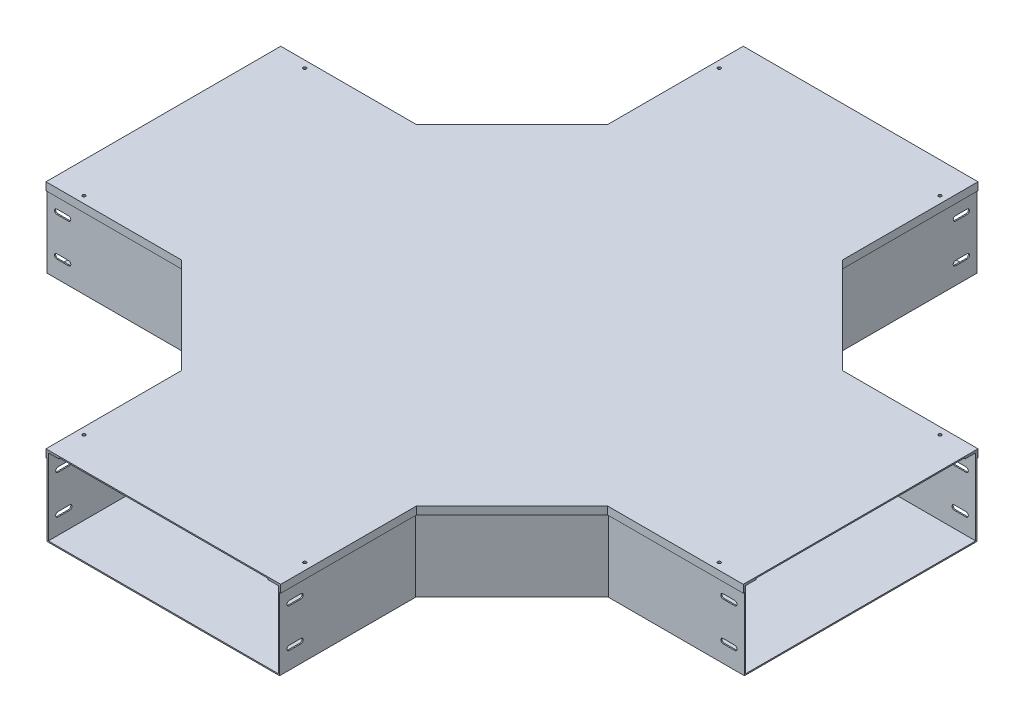
SolidWorks part; units mm, degrees
material "Plain Carbon Steel"
ref_plane "Front Plane" through (0, 0, 0) normal (0, 0, 1) x (1, 0, 0)
ref_plane "Top Plane" through (0, 0, 0) normal (0, 1, 0) x (1, 0, 0)
ref_plane "Right Plane" through (0, 0, 0) normal (1, 0, 0) x (0, 0, -1)
ref_plane "Plane1" through (0, -50, 0) normal (0, 1, 0) x (1, 0, 0)
sketch "Sketch1" plane through (0, -50, 0) normal (0, 1, 0) x (1, 0, 0)
  line L0 (-150, 450) -> (150, 450)
  line L1 (-150, -450) -> (150, -450)
  line L2 (450, 150) -> (450, -150)
  line L3 (-450, 150) -> (-450, -150)
  line L4 (150, -450) -> (150, -274.2641)
  line L5 (450, -150) -> (274.2641, -150)
  line L6 (150, 450) -> (150, 274.2641)
  line L7 (-150, 450) -> (-150, 274.2641)
  line L8 (-450, 150) -> (-274.2641, 150)
  line L9 (-450, -150) -> (-274.2641, -150)
  line L10 (-150, -450) -> (-150, -274.2641)
  line L11 (450, 150) -> (274.2641, 150)
  line L12 (0, 450) -> (0, -450) construction
  line L13 (-450, 0) -> (450, 0) construction
  line L14 (150, 274.2641) -> (274.2641, 150)
  line L15 (-274.2641, 150) -> (-150, 274.2641)
  line L16 (-274.2641, -150) -> (-150, -274.2641)
  line L17 (150, -274.2641) -> (274.2641, -150)
  dimension "Width" = 300
  dimension "Length" = 900
extrude "Boss-Extrude1" add sketch "Sketch1" along normal blind 1.5
sketch "Sketch2" plane through (0, -50, 0) normal (0, -1, 0) x (-1, 0, 0)
  line L0 (-150, -450) -> (-150, -274.2641) construction
  line L1 (-274.2641, -150) -> (-450, -150) construction
  line L2 (-150, -450) -> (-150, -274.2641)
  line L3 (-274.2641, -150) -> (-450, -150)
  line L4 (-450, 150) -> (-274.2641, 150) construction
  line L5 (-150, 274.2641) -> (-150, 450) construction
  line L6 (150, 450) -> (150, 274.2641) construction
  line L7 (274.2641, 150) -> (450, 150) construction
  line L8 (450, -150) -> (274.2641, -150) construction
  line L9 (150, -274.2641) -> (150, -450) construction
  line L10 (-450, 150) -> (-274.2641, 150)
  line L11 (-150, 274.2641) -> (-150, 450)
  line L12 (150, 450) -> (150, 274.2641)
  line L13 (274.2641, 150) -> (450, 150)
  line L14 (450, -150) -> (274.2641, -150)
  line L15 (150, -274.2641) -> (150, -450)
  line L16 (274.2641, 150) -> (150, 274.2641)
  line L17 (274.2641, -150) -> (150, -274.2641)
  line L18 (-150, -274.2641) -> (-274.2641, -150)
  line L19 (-274.2641, 150) -> (-150, 274.2641)
extrude "Extrude-Thin1" add sketch "Sketch2" against normal blind 100 thin thin type one direction wall 1.5
sketch "Sketch3" plane through (0, 0, 0) normal (0, 0, 1) x (1, 0, 0)
  line L0 (422.5, 25) -> (437.5, 25) construction
  line L1 (422.5, 28) -> (437.5, 28)
  line L2 (422.5, 22) -> (437.5, 22)
  line L3 (422.5, -25) -> (437.5, -25) construction
  line L4 (422.5, -22) -> (437.5, -22)
  line L5 (422.5, -28) -> (437.5, -28)
  line L6 (410, 0) -> (450, 0) construction
  line L7 (450, -48.5) -> (450, 50) construction
  line L8 (-437.5, 25) -> (-422.5, 25) construction
  line L9 (430, -50) -> (430, 0) construction
  line L10 (-437.5, 28) -> (-422.5, 28)
  line L11 (430, 0) -> (430, 50) construction
  line L12 (-437.5, 22) -> (-422.5, 22)
  line L13 (-437.5, -25) -> (-422.5, -25) construction
  line L14 (-437.5, -22) -> (-422.5, -22)
  line L15 (-437.5, -28) -> (-422.5, -28)
  line L16 (-450, 0) -> (-410, 0) construction
  line L17 (-430, -50) -> (-430, 0) construction
  line L18 (-430, 0) -> (-430, 50) construction
  line L19 (-450, 50) -> (-450, -48.5) construction
  arc A0 (422.5, 28) -> (422.5, 22) centre (422.5, 25) ccw
  arc A1 (437.5, 22) -> (437.5, 28) centre (437.5, 25) ccw
  arc A2 (422.5, -22) -> (422.5, -28) centre (422.5, -25) ccw
  arc A3 (437.5, -28) -> (437.5, -22) centre (437.5, -25) ccw
  arc A4 (-437.5, 28) -> (-437.5, 22) centre (-437.5, 25) ccw
  arc A5 (-422.5, 22) -> (-422.5, 28) centre (-422.5, 25) ccw
  arc A6 (-437.5, -22) -> (-437.5, -28) centre (-437.5, -25) ccw
  arc A7 (-422.5, -28) -> (-422.5, -22) centre (-422.5, -25) ccw
  point P2 (430, 25)
  point P8 (430, -25)
  point P22 (-430, 25)
  point P30 (-430, -25)
  dimension "D1" = 3
  dimension "D2" = 15
  dimension "D3" = 50
  dimension "D4" = 40
  dimension "D5" = 50
extrude "Cut-Extrude1" cut sketch "Sketch3" against normal through all and the other way through all
sketch "Sketch4" plane through (0, 0, 0) normal (1, 0, 0) x (0, 0, -1)
  line L0 (-450, 0) -> (-410, 0) construction
  line L1 (-450, -48.5) -> (-450, 50) construction
  line L2 (410, 0) -> (450, 0) construction
  line L3 (-430, 50) -> (-430, 0) construction
  line L4 (430, 50) -> (430, 0) construction
  line L5 (-430, 0) -> (-430, -50) construction
  line L6 (430, 0) -> (430, -50) construction
  line L7 (-437.5, 25) -> (-422.5, 25) construction
  line L8 (-437.5, 28) -> (-422.5, 28)
  line L9 (-437.5, 22) -> (-422.5, 22)
  line L10 (-437.5, -25) -> (-422.5, -25) construction
  line L11 (-437.5, -22) -> (-422.5, -22)
  line L12 (-437.5, -28) -> (-422.5, -28)
  line L13 (422.5, 25) -> (437.5, 25) construction
  line L14 (422.5, 28) -> (437.5, 28)
  line L15 (422.5, 22) -> (437.5, 22)
  line L16 (422.5, -25) -> (437.5, -25) construction
  line L17 (422.5, -22) -> (437.5, -22)
  line L18 (422.5, -28) -> (437.5, -28)
  line L19 (450, 50) -> (450, -48.5) construction
  arc A0 (-437.5, 28) -> (-437.5, 22) centre (-437.5, 25) ccw
  arc A1 (-422.5, 22) -> (-422.5, 28) centre (-422.5, 25) ccw
  arc A2 (-437.5, -22) -> (-437.5, -28) centre (-437.5, -25) ccw
  arc A3 (-422.5, -28) -> (-422.5, -22) centre (-422.5, -25) ccw
  arc A4 (422.5, 28) -> (422.5, 22) centre (422.5, 25) ccw
  arc A5 (437.5, 22) -> (437.5, 28) centre (437.5, 25) ccw
  arc A6 (422.5, -22) -> (422.5, -28) centre (422.5, -25) ccw
  arc A7 (437.5, -28) -> (437.5, -22) centre (437.5, -25) ccw
  point P15 (-430, 25)
  point P21 (-430, -25)
  point P29 (430, 25)
  point P35 (430, -25)
  dimension "D1" = 3
  dimension "D2" = 15
  dimension "D5" = 50
  dimension "D3" = 40
  dimension "D4" = 50
extrude "Cut-Extrude2" cut sketch "Sketch4" against normal through all and the other way through all
sketch "Sketch5" plane through (0, 50, 0) normal (0, 1, 0) x (1, 0, 0)
  line L0 (450, 135) -> (268.0509, 135)
  line L1 (268.0509, 135) -> (135, 268.0509)
  line L2 (135, 268.0509) -> (135, 450)
  line L3 (-135, 450) -> (-135, 268.0509)
  line L4 (-135, 268.0509) -> (-268.0509, 135)
  line L5 (-268.0509, 135) -> (-450, 135)
  line L6 (-450, -135) -> (-268.0509, -135)
  line L7 (-268.0509, -135) -> (-135, -268.0509)
  line L8 (-135, -268.0509) -> (-135, -450)
  line L9 (135, -450) -> (135, -268.0509)
  line L10 (135, -268.0509) -> (268.0509, -135)
  line L11 (268.0509, -135) -> (450, -135)
  line L12 (-450, -150) -> (-450, -135)
  line L13 (-450, 135) -> (-450, 150)
  line L14 (-135, 450) -> (-150, 450)
  line L15 (150, 450) -> (135, 450)
  line L16 (274.2641, 150) -> (150, 274.2641)
  line L17 (150, 274.2641) -> (150, 450)
  line L18 (150, 450) -> (-150, 450)
  line L19 (-150, 450) -> (-150, 274.2641)
  line L20 (-150, 274.2641) -> (-274.2641, 150)
  line L21 (-274.2641, 150) -> (-450, 150)
  line L22 (-450, 150) -> (-450, -150)
  line L23 (-450, -150) -> (-274.2641, -150)
  line L24 (-274.2641, -150) -> (-150, -274.2641)
  line L25 (-150, -274.2641) -> (-150, -450)
  line L26 (-150, -450) -> (150, -450)
  line L27 (150, -450) -> (150, -274.2641)
  line L28 (150, -274.2641) -> (274.2641, -150)
  line L29 (274.2641, -150) -> (450, -150)
  line L30 (450, -150) -> (450, 150)
  line L31 (450, 150) -> (274.2641, 150)
  line L32 (274.2641, 150) -> (150, 274.2641)
  line L33 (150, 274.2641) -> (150, 450)
  line L34 (450, 135) -> (450, 150)
  line L35 (-150, 450) -> (-150, 274.2641)
  line L36 (-150, 274.2641) -> (-274.2641, 150)
  line L37 (-274.2641, 150) -> (-450, 150)
  line L38 (450, -150) -> (450, -135)
  line L39 (-450, -150) -> (-274.2641, -150)
  line L40 (-274.2641, -150) -> (-150, -274.2641)
  line L41 (-150, -274.2641) -> (-150, -450)
  line L42 (135, -450) -> (150, -450)
  line L43 (150, -450) -> (150, -274.2641)
  line L44 (150, -274.2641) -> (274.2641, -150)
  line L45 (274.2641, -150) -> (450, -150)
  line L46 (-150, -450) -> (-135, -450)
  line L47 (450, 150) -> (274.2641, 150)
  dimension "D1" = 0
  dimension "D2" = 15
extrude "Boss-Extrude2" add sketch "Sketch5" along normal blind 1.5
sketch "Sketch6" plane through (0, 51.5, 0) normal (0, 1, 0) x (1, 0, 0)
  line L0 (-450, 150) -> (-450, 135) construction
  line L1 (-450, -135) -> (-450, -150) construction
  line L2 (450, 135) -> (450, 150) construction
  line L3 (450, -150) -> (450, -135) construction
  line L4 (-150, -450) -> (-135, -450) construction
  line L5 (135, -450) -> (150, -450) construction
  line L6 (-135, 450) -> (-150, 450) construction
  line L7 (150, 450) -> (135, 450) construction
  circle A0 centre (-410, -142.5) radius 2
  circle A1 centre (-410, 142.5) radius 2
  circle A2 centre (-142.5, 410) radius 2
  circle A3 centre (142.5, 410) radius 2
  circle A4 centre (410, 142.5) radius 2
  circle A5 centre (410, -142.5) radius 2
  circle A6 centre (142.5, -410) radius 2
  circle A7 centre (-142.5, -410) radius 2
  point P18 (-450, 142.5)
  point P21 (-450, -142.5)
  point P24 (450, 142.5)
  point P27 (450, -142.5)
  point P32 (142.5, -450)
  point P33 (-142.5, -450)
  point P36 (-142.5, 450)
  point P39 (142.5, 450)
  dimension "D1" = 40
  dimension "D5" = 4
  dimension "D2" = 40
  dimension "D3" = 40
  dimension "D4" = 40
extrude "Cut-Extrude3" cut sketch "Sketch6" against normal up to next
sketch "Sketch7" plane through (0, 51.5, 0) normal (0, 1, 0) x (1, 0, 0)
  line L16 (274.2641, 150) -> (150, 274.2641)
  line L17 (150, 274.2641) -> (150, 450)
  line L18 (150, 450) -> (-150, 450)
  line L19 (-150, 450) -> (-150, 274.2641)
  line L20 (-150, 274.2641) -> (-274.2641, 150)
  line L21 (-274.2641, 150) -> (-450, 150)
  line L22 (-450, 150) -> (-450, -150)
  line L23 (-450, -150) -> (-274.2641, -150)
  line L24 (-274.2641, -150) -> (-150, -274.2641)
  line L25 (-150, -274.2641) -> (-150, -450)
  line L26 (-150, -450) -> (150, -450)
  line L27 (150, -450) -> (150, -274.2641)
  line L28 (150, -274.2641) -> (274.2641, -150)
  line L29 (274.2641, -150) -> (450, -150)
  line L30 (450, -150) -> (450, 150)
  line L31 (450, 150) -> (274.2641, 150)
  line L32 (274.2641, 150) -> (150, 274.2641)
  line L33 (150, 274.2641) -> (150, 450)
  line L34 (150, 450) -> (-150, 450)
  line L35 (-150, 450) -> (-150, 274.2641)
  line L36 (-150, 274.2641) -> (-274.2641, 150)
  line L37 (-274.2641, 150) -> (-450, 150)
  line L38 (-450, 150) -> (-450, -150)
  line L39 (-450, -150) -> (-274.2641, -150)
  line L40 (-274.2641, -150) -> (-150, -274.2641)
  line L41 (-150, -274.2641) -> (-150, -450)
  line L42 (-150, -450) -> (150, -450)
  line L43 (150, -450) -> (150, -274.2641)
  line L44 (150, -274.2641) -> (274.2641, -150)
  line L45 (274.2641, -150) -> (450, -150)
  line L46 (450, -150) -> (450, 150)
  line L47 (450, 150) -> (274.2641, 150)
  dimension "D1" = 0
extrude "Boss-Extrude3" add sketch "Sketch7" along normal blind 1.5 separate body
sketch "Sketch8" plane through (0, 53, 0) normal (0, 1, 0) x (1, 0, 0)
  line L0 (150, 274.2641) -> (150, 450) construction
  line L1 (274.2641, 150) -> (150, 274.2641) construction
  line L2 (450, 150) -> (274.2641, 150) construction
  line L3 (274.2641, -150) -> (450, -150) construction
  line L4 (150, -274.2641) -> (274.2641, -150) construction
  line L5 (150, -450) -> (150, -274.2641) construction
  line L6 (-150, -274.2641) -> (-150, -450) construction
  line L7 (-274.2641, -150) -> (-150, -274.2641) construction
  line L8 (-450, -150) -> (-274.2641, -150) construction
  line L9 (-274.2641, 150) -> (-450, 150) construction
  line L10 (-150, 274.2641) -> (-274.2641, 150) construction
  line L11 (-150, 450) -> (-150, 274.2641) construction
  line L12 (150, 274.2641) -> (150, 450)
  line L13 (274.2641, 150) -> (150, 274.2641)
  line L14 (450, 150) -> (274.2641, 150)
  line L15 (274.2641, -150) -> (450, -150)
  line L16 (150, -274.2641) -> (274.2641, -150)
  line L17 (150, -450) -> (150, -274.2641)
  line L18 (-150, -274.2641) -> (-150, -450)
  line L19 (-274.2641, -150) -> (-150, -274.2641)
  line L20 (-450, -150) -> (-274.2641, -150)
  line L21 (-274.2641, 150) -> (-450, 150)
  line L22 (-150, 274.2641) -> (-274.2641, 150)
  line L23 (-150, 450) -> (-150, 274.2641)
extrude "Extrude-Thin2" add sketch "Sketch8" against normal blind 10 thin thin type one direction wall 1.5
sketch "Sketch9" plane through (0, 53, 0) normal (0, 1, 0) x (1, 0, 0)
  circle A1 centre (-142.5, -410) radius 2
  circle A2 centre (-142.5, -410) radius 2
  circle A3 centre (142.5, -410) radius 2
  circle A4 centre (142.5, -410) radius 2
  circle A5 centre (410, -142.5) radius 2
  circle A6 centre (410, -142.5) radius 2
  circle A7 centre (410, 142.5) radius 2
  circle A8 centre (410, 142.5) radius 2
  circle A9 centre (142.5, 410) radius 2
  circle A10 centre (142.5, 410) radius 2
  circle A11 centre (-142.5, 410) radius 2
  circle A12 centre (-142.5, 410) radius 2
  circle A13 centre (-410, 142.5) radius 2
  circle A14 centre (-410, 142.5) radius 2
  circle A15 centre (-410, -142.5) radius 2
  circle A16 centre (-410, -142.5) radius 2
  dimension "D1" = 0
  dimension "D2" = 0
  dimension "D3" = 0
  dimension "D4" = 0
  dimension "D5" = 0
  dimension "D6" = 0
  dimension "D7" = 0
  dimension "D8" = 0
extrude "Cut-Extrude4" cut sketch "Sketch9" against normal up to next (1.5 mm away)
sketch "Sketch10" plane through (0, 0, 0) normal (0, -1, 0) x (-1, 0, 0)
  line L0 (150, -450) -> (-150, -450) construction
  line L1 (-450, -150) -> (-450, 150) construction
  line L2 (150, 450) -> (-150, 450) construction
  line L3 (450, -150) -> (450, 150) construction
  point P0 (0, -450)
  point P1 (-450, 0)
  point P4 (0, 450)
  point P7 (450, 0)
  point P10 (0, 0)
other "CPoint1" parameters "Diameter"=10, "StubLength"=300
ref_axis "Axis1" through (460, 0, 0) along (-1, 0, 0)
other "CPoint2" parameters "Diameter"=10, "StubLength"=300
ref_axis "Axis2" through (-460, 0, 0) along (1, 0, 0)
other "CPoint3" parameters "Diameter"=10, "StubLength"=300
ref_axis "Axis3" through (0, 0, 460) along (0, 0, -1)
other "CPoint4" parameters "Diameter"=10, "StubLength"=300
ref_axis "Axis4" through (0, 0, -460) along (0, 0, 1)
other "RPoint1"
equation "\"D5@Extrude-Thin1\"=\"Thickness@Boss-Extrude1\""
equation "\"D3@Sketch3\"=\"Height@Extrude-Thin1\"/2"
equation "\"D5@Sketch3\"=\"Height@Extrude-Thin1\"/2"
equation "\"D4@Sketch4\"=\"Height@Extrude-Thin1\"/2"
equation "\"D5@Sketch4\"=\"Height@Extrude-Thin1\"/2"
equation "\"Thickness@Boss-Extrude2\"=\"Thickness@Boss-Extrude1\""
equation "\"Thickness@Boss-Extrude3\"=\"Thickness@Boss-Extrude1\""
